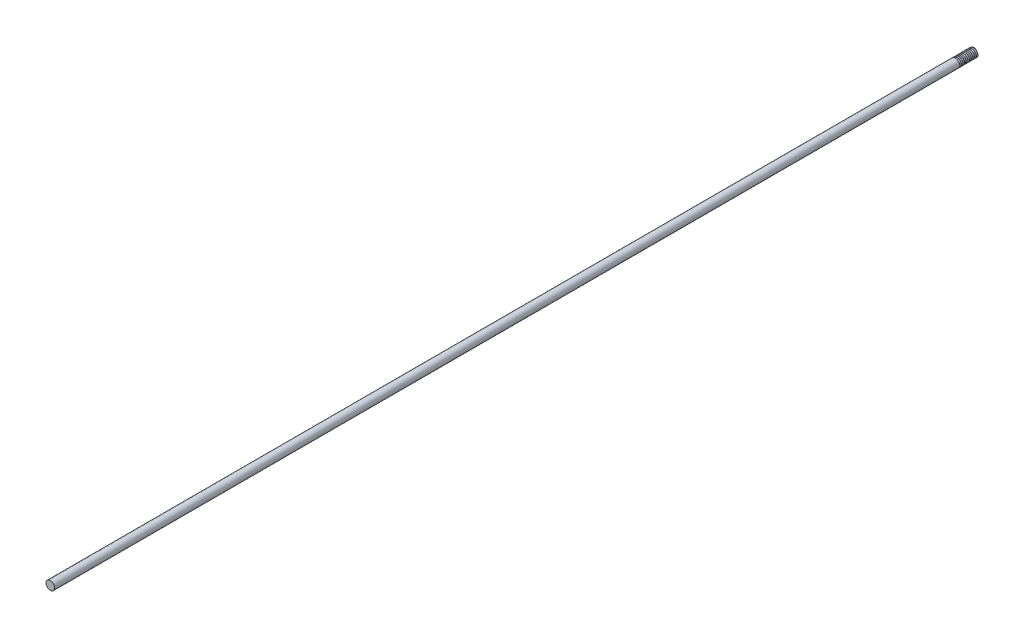
SolidWorks part; units mm, degrees
ref_plane "Front Plane" through (0, 0, 0) normal (0, 0, 1) x (1, 0, 0)
ref_plane "Top Plane" through (0, 0, 0) normal (0, 1, 0) x (1, 0, 0)
ref_plane "Right Plane" through (0, 0, 0) normal (1, 0, 0) x (0, 0, -1)
sketch "Sketch1" plane through (0, 0, 0) normal (0, 0, 1) x (1, 0, 0)
  circle A0 centre (0, 0) radius 1.1811
  dimension "D1" = 2.3622
extrude "Rod" add sketch "Sketch1" along normal blind 254
ref_plane "Plane1" through (0, 0, -1.27) normal (0, 0, -1) x (-1, 0, 0)
sketch "Sketch3" plane through (0, 0, -1.27) normal (0, 0, -1) x (-1, 0, 0)
  circle A0 centre (0, 0) radius 1.1811 construction
  circle A1 centre (0, 0) radius 1.1811
curve "Helix/Spiral1" pitch 0.4536 height 6.35 radius 1.1811 centre (0, 0, -1.27) axis (0, 0, 1) start towards (0, 1, 0)
sketch "Sketch4" plane through (0, 0, 0) normal (1, 0, 0) x (0, 0, -1)
  line L0 (1.0433, 1.2302) -> (1.4967, 1.2302)
  line L1 (1.4967, 1.2302) -> (1.27, 0.8375)
  line L2 (1.27, 0.8375) -> (1.0433, 1.2302)
  line L3 (1.27, 0.8375) -> (1.27, 1.2302) construction
  spline S0 degree 3 poles (-75.4369, -1997.273) (3.0387, -191.216) (2.0286, 8.4213) (1.2133, 0.8569) (1.185, 0.4638) (1.1566, 0) (1.1283, -0.4638) (1.0999, -0.8569) (1.0716, -1.1196) (1.0432, -1.2118) (1.0149, -1.1196) (0.9865, -0.8569) (0.9582, -0.4638) (0.9298, 0) (0.9015, 0.4638) (0.8731, 0.8569) (0.8448, 1.1196) (0.8164, 1.2118) (0.7881, 1.1196) (0.7597, 0.8569) (0.7314, 0.4638) (0.703, 0) (0.6747, -0.4638) (0.6463, -0.8569) (0.618, -1.1196) (0.5896, -1.2118) (0.5613, -1.1196) (0.5329, -0.8569) (0.5046, -0.4638) (0.4763, 0) (0.4479, 0.4638) (0.4196, 0.8569) (0.3912, 1.1196) (0.3629, 1.2118) (0.3345, 1.1196) (0.3062, 0.8569) (0.2778, 0.4638) (0.2495, 0) (0.2211, -0.4638) (0.1928, -0.8569) (0.1644, -1.1196) (0.1361, -1.2118) (0.1077, -1.1196) (0.0794, -0.8569) (0.051, -0.4638) (0.0227, 0) (-0.0057, 0.4638) (-0.034, 0.8569) (-0.0624, 1.1196) (-0.0907, 1.2118) (-0.1191, 1.1196) (-0.1474, 0.8569) (-0.1758, 0.4638) (-0.2041, 0) (-0.2325, -0.4638) (-0.2608, -0.8569) (-0.2892, -1.1196) (-0.3175, -1.2118) (-0.3458, -1.1196) (-0.3742, -0.8569) (-0.4025, -0.4638) (-0.4309, 0) (-0.4592, 0.4638) (-0.4876, 0.8569) (-0.5159, 1.1196) (-0.5443, 1.2118) (-0.5726, 1.1196) (-0.601, 0.8569) (-0.6293, 0.4638) (-0.6577, 0) (-0.686, -0.4638) (-0.7144, -0.8569) (-0.7427, -1.1196) (-0.7711, -1.2118) (-0.7994, -1.1196) (-0.8278, -0.8569) (-0.8561, -0.4638) (-0.8845, 0) (-0.9128, 0.4638) (-0.9412, 0.8569) (-0.9695, 1.1196) (-0.9979, 1.2118) (-1.0262, 1.1196) (-1.0546, 0.8569) (-1.0829, 0.4638) (-1.1112, 0) (-1.1396, -0.4638) (-1.1679, -0.8569) (-1.1963, -1.1196) (-1.2246, -1.2118) (-1.253, -1.1196) (-1.2813, -0.8569) (-1.3097, -0.4638) (-1.338, 0) (-1.3664, 0.4638) (-1.3947, 0.8569) (-1.4231, 1.1196) (-1.4514, 1.2118) (-1.4798, 1.1196) (-1.5081, 0.8569) (-1.5365, 0.4638) (-1.5648, 0) (-1.5932, -0.4638) (-1.6215, -0.8569) (-1.6499, -1.1196) (-1.6782, -1.2118) (-1.7066, -1.1196) (-1.7349, -0.8569) (-1.7633, -0.4638) (-1.7916, 0) (-1.82, 0.4638) (-1.8483, 0.8569) (-1.8767, 1.1196) (-1.905, 1.2118) (-1.9333, 1.1196) (-1.9617, 0.8569) (-1.99, 0.4638) (-2.0184, 0) (-2.0467, -0.4638) (-2.0751, -0.8569) (-2.1034, -1.1196) (-2.1318, -1.2118) (-2.1601, -1.1196) (-2.1885, -0.8569) (-2.2168, -0.4638) (-2.2452, 0) (-2.2735, 0.4638) (-2.3019, 0.8569) (-2.3302, 1.1196) (-2.3586, 1.2118) (-2.3869, 1.1196) (-2.4153, 0.8569) (-2.4436, 0.4638) (-2.472, 0) (-2.5003, -0.4638) (-2.5287, -0.8569) (-2.557, -1.1196) (-2.5854, -1.2118) (-2.6137, -1.1196) (-2.6421, -0.8569) (-2.6704, -0.4638) (-2.6987, 0) (-2.7271, 0.4638) (-2.7554, 0.8569) (-2.7838, 1.1196) (-2.8121, 1.2118) (-2.8405, 1.1196) (-2.8688, 0.8569) (-2.8972, 0.4638) (-2.9255, 0) (-2.9539, -0.4638) (-2.9822, -0.8569) (-3.0106, -1.1196) (-3.0389, -1.2118) (-3.0673, -1.1196) (-3.0956, -0.8569) (-3.124, -0.4638) (-3.1523, 0) (-3.1807, 0.4638) (-3.209, 0.8569) (-3.2374, 1.1196) (-3.2657, 1.2118) (-3.2941, 1.1196) (-3.3224, 0.8569) (-3.3508, 0.4638) (-3.3791, 0) (-3.4075, -0.4638) (-3.4358, -0.8569) (-3.4642, -1.1196) (-3.4925, -1.2118) (-3.5208, -1.1196) (-3.5492, -0.8569) (-3.5775, -0.4638) (-3.6059, 0) (-3.6342, 0.4638) (-3.6626, 0.8569) (-3.6909, 1.1196) (-3.7193, 1.2118) (-3.7476, 1.1196) (-3.776, 0.8569) (-3.8043, 0.4638) (-3.8327, 0) (-3.861, -0.4638) (-3.8894, -0.8569) (-3.9177, -1.1196) (-3.9461, -1.2118) (-3.9744, -1.1196) (-4.0028, -0.8569) (-4.0311, -0.4638) (-4.0595, 0) (-4.0878, 0.4638) (-4.1162, 0.8569) (-4.1445, 1.1196) (-4.1729, 1.2118) (-4.2012, 1.1196) (-4.2296, 0.8569) (-4.2579, 0.4638) (-4.2862, 0) (-4.3146, -0.4638) (-4.3429, -0.8569) (-4.3713, -1.1196) (-4.3996, -1.2118) (-4.428, -1.1196) (-4.4563, -0.8569) (-4.4847, -0.4638) (-4.513, 0) (-4.5414, 0.4638) (-4.5697, 0.8569) (-4.5981, 1.1196) (-4.6264, 1.2118) (-4.6548, 1.1196) (-4.6831, 0.8569) (-4.7115, 0.4638) (-4.7398, 0) (-4.7682, -0.4638) (-4.7965, -0.8569) (-4.8249, -1.1196) (-4.8532, -1.2118) (-4.8816, -1.1196) (-4.9099, -0.8569) (-4.9383, -0.4638) (-4.9666, 0) (-4.995, 0.4638) (-5.0233, 0.8569) (-5.8386, 8.4211) (-6.8487, -191.2103) (71.6235, -1997.1954) knots -0.372256 -0.372256 -0.372256 -0.372256 0.004464 0.008929 0.013393 0.017857 0.022321 0.026786 0.03125 0.035714 0.040179 0.044643 0.049107 0.053571 0.058036 0.0625 0.066964 0.071429 0.075893 0.080357 0.084821 0.089286 0.09375 0.098214 0.102679 0.107143 0.111607 0.116071 0.120536 0.125 0.129464 0.133929 0.138393 0.142857 0.147321 0.151786 0.15625 0.160714 0.165179 0.169643 0.174107 0.178571 0.183036 0.1875 0.191964 0.196429 0.200893 0.205357 0.209821 0.214286 0.21875 0.223214 0.227679 0.232143 0.236607 0.241071 0.245536 0.25 0.254464 0.258929 0.263393 0.267857 0.272321 0.276786 0.28125 0.285714 0.290179 0.294643 0.299107 0.303571 0.308036 0.3125 0.316964 0.321429 0.325893 0.330357 0.334821 0.339286 0.34375 0.348214 0.352679 0.357143 0.361607 0.366071 0.370536 0.375 0.379464 0.383929 0.388393 0.392857 0.397321 0.401786 0.40625 0.410714 0.415179 0.419643 0.424107 0.428571 0.433036 0.4375 0.441964 0.446429 0.450893 0.455357 0.459821 0.464286 0.46875 0.473214 0.477679 0.482143 0.486607 0.491071 0.495536 0.5 0.504464 0.508929 0.513393 0.517857 0.522321 0.526786 0.53125 0.535714 0.540179 0.544643 0.549107 0.553571 0.558036 0.5625 0.566964 0.571429 0.575893 0.580357 0.584821 0.589286 0.59375 0.598214 0.602679 0.607143 0.611607 0.616071 0.620536 0.625 0.629464 0.633929 0.638393 0.642857 0.647321 0.651786 0.65625 0.660714 0.665179 0.669643 0.674107 0.678571 0.683036 0.6875 0.691964 0.696429 0.700893 0.705357 0.709821 0.714286 0.71875 0.723214 0.727679 0.732143 0.736607 0.741071 0.745536 0.75 0.754464 0.758929 0.763393 0.767857 0.772321 0.776786 0.78125 0.785714 0.790179 0.794643 0.799107 0.803571 0.808036 0.8125 0.816964 0.821429 0.825893 0.830357 0.834821 0.839286 0.84375 0.848214 0.852679 0.857143 0.861607 0.866071 0.870536 0.875 0.879464 0.883929 0.888393 0.892857 0.897321 0.901786 0.90625 0.910714 0.915179 0.919643 0.924107 0.928571 0.933036 0.9375 0.941964 0.946429 0.950893 0.955357 0.959821 0.964286 0.96875 0.973214 0.977679 0.982143 0.986607 0.991071 0.995536 1.37225 1.37225 1.37225 1.37225 only from (1.27, 1.1811) to (-5.08, 1.1811) construction
  spline S1 degree 3 poles (1.27, 1.1811) (1.2606, 1.1811) (1.2416, 1.1196) (1.2133, 0.8569) (1.185, 0.4638) (1.1566, 0) (1.1283, -0.4638) (1.0999, -0.8569) (1.0716, -1.1196) (1.0432, -1.2118) (1.0149, -1.1196) (0.9865, -0.8569) (0.9582, -0.4638) (0.9298, 0) (0.9015, 0.4638) (0.8731, 0.8569) (0.8448, 1.1196) (0.8164, 1.2118) (0.7881, 1.1196) (0.7597, 0.8569) (0.7314, 0.4638) (0.703, 0) (0.6747, -0.4638) (0.6463, -0.8569) (0.618, -1.1196) (0.5896, -1.2118) (0.5613, -1.1196) (0.5329, -0.8569) (0.5046, -0.4638) (0.4763, 0) (0.4479, 0.4638) (0.4196, 0.8569) (0.3912, 1.1196) (0.3629, 1.2118) (0.3345, 1.1196) (0.3062, 0.8569) (0.2778, 0.4638) (0.2495, 0) (0.2211, -0.4638) (0.1928, -0.8569) (0.1644, -1.1196) (0.1361, -1.2118) (0.1077, -1.1196) (0.0794, -0.8569) (0.051, -0.4638) (0.0227, 0) (-0.0057, 0.4638) (-0.034, 0.8569) (-0.0624, 1.1196) (-0.0907, 1.2118) (-0.1191, 1.1196) (-0.1474, 0.8569) (-0.1758, 0.4638) (-0.2041, 0) (-0.2325, -0.4638) (-0.2608, -0.8569) (-0.2892, -1.1196) (-0.3175, -1.2118) (-0.3458, -1.1196) (-0.3742, -0.8569) (-0.4025, -0.4638) (-0.4309, 0) (-0.4592, 0.4638) (-0.4876, 0.8569) (-0.5159, 1.1196) (-0.5443, 1.2118) (-0.5726, 1.1196) (-0.601, 0.8569) (-0.6293, 0.4638) (-0.6577, 0) (-0.686, -0.4638) (-0.7144, -0.8569) (-0.7427, -1.1196) (-0.7711, -1.2118) (-0.7994, -1.1196) (-0.8278, -0.8569) (-0.8561, -0.4638) (-0.8845, 0) (-0.9128, 0.4638) (-0.9412, 0.8569) (-0.9695, 1.1196) (-0.9979, 1.2118) (-1.0262, 1.1196) (-1.0546, 0.8569) (-1.0829, 0.4638) (-1.1112, 0) (-1.1396, -0.4638) (-1.1679, -0.8569) (-1.1963, -1.1196) (-1.2246, -1.2118) (-1.253, -1.1196) (-1.2813, -0.8569) (-1.3097, -0.4638) (-1.338, 0) (-1.3664, 0.4638) (-1.3947, 0.8569) (-1.4231, 1.1196) (-1.4514, 1.2118) (-1.4798, 1.1196) (-1.5081, 0.8569) (-1.5365, 0.4638) (-1.5648, 0) (-1.5932, -0.4638) (-1.6215, -0.8569) (-1.6499, -1.1196) (-1.6782, -1.2118) (-1.7066, -1.1196) (-1.7349, -0.8569) (-1.7633, -0.4638) (-1.7916, 0) (-1.82, 0.4638) (-1.8483, 0.8569) (-1.8767, 1.1196) (-1.905, 1.2118) (-1.9333, 1.1196) (-1.9617, 0.8569) (-1.99, 0.4638) (-2.0184, 0) (-2.0467, -0.4638) (-2.0751, -0.8569) (-2.1034, -1.1196) (-2.1318, -1.2118) (-2.1601, -1.1196) (-2.1885, -0.8569) (-2.2168, -0.4638) (-2.2452, 0) (-2.2735, 0.4638) (-2.3019, 0.8569) (-2.3302, 1.1196) (-2.3586, 1.2118) (-2.3869, 1.1196) (-2.4153, 0.8569) (-2.4436, 0.4638) (-2.472, 0) (-2.5003, -0.4638) (-2.5287, -0.8569) (-2.557, -1.1196) (-2.5854, -1.2118) (-2.6137, -1.1196) (-2.6421, -0.8569) (-2.6704, -0.4638) (-2.6987, 0) (-2.7271, 0.4638) (-2.7554, 0.8569) (-2.7838, 1.1196) (-2.8121, 1.2118) (-2.8405, 1.1196) (-2.8688, 0.8569) (-2.8972, 0.4638) (-2.9255, 0) (-2.9539, -0.4638) (-2.9822, -0.8569) (-3.0106, -1.1196) (-3.0389, -1.2118) (-3.0673, -1.1196) (-3.0956, -0.8569) (-3.124, -0.4638) (-3.1523, 0) (-3.1807, 0.4638) (-3.209, 0.8569) (-3.2374, 1.1196) (-3.2657, 1.2118) (-3.2941, 1.1196) (-3.3224, 0.8569) (-3.3508, 0.4638) (-3.3791, 0) (-3.4075, -0.4638) (-3.4358, -0.8569) (-3.4642, -1.1196) (-3.4925, -1.2118) (-3.5208, -1.1196) (-3.5492, -0.8569) (-3.5775, -0.4638) (-3.6059, 0) (-3.6342, 0.4638) (-3.6626, 0.8569) (-3.6909, 1.1196) (-3.7193, 1.2118) (-3.7476, 1.1196) (-3.776, 0.8569) (-3.8043, 0.4638) (-3.8327, 0) (-3.861, -0.4638) (-3.8894, -0.8569) (-3.9177, -1.1196) (-3.9461, -1.2118) (-3.9744, -1.1196) (-4.0028, -0.8569) (-4.0311, -0.4638) (-4.0595, 0) (-4.0878, 0.4638) (-4.1162, 0.8569) (-4.1445, 1.1196) (-4.1729, 1.2118) (-4.2012, 1.1196) (-4.2296, 0.8569) (-4.2579, 0.4638) (-4.2862, 0) (-4.3146, -0.4638) (-4.3429, -0.8569) (-4.3713, -1.1196) (-4.3996, -1.2118) (-4.428, -1.1196) (-4.4563, -0.8569) (-4.4847, -0.4638) (-4.513, 0) (-4.5414, 0.4638) (-4.5697, 0.8569) (-4.5981, 1.1196) (-4.6264, 1.2118) (-4.6548, 1.1196) (-4.6831, 0.8569) (-4.7115, 0.4638) (-4.7398, 0) (-4.7682, -0.4638) (-4.7965, -0.8569) (-4.8249, -1.1196) (-4.8532, -1.2118) (-4.8816, -1.1196) (-4.9099, -0.8569) (-4.9383, -0.4638) (-4.9666, 0) (-4.995, 0.4638) (-5.0233, 0.8569) (-5.0516, 1.1196) (-5.0706, 1.1811) (-5.08, 1.1811) knots 0 0 0 0 0.004464 0.008929 0.013393 0.017857 0.022321 0.026786 0.03125 0.035714 0.040179 0.044643 0.049107 0.053571 0.058036 0.0625 0.066964 0.071429 0.075893 0.080357 0.084821 0.089286 0.09375 0.098214 0.102679 0.107143 0.111607 0.116071 0.120536 0.125 0.129464 0.133929 0.138393 0.142857 0.147321 0.151786 0.15625 0.160714 0.165179 0.169643 0.174107 0.178571 0.183036 0.1875 0.191964 0.196429 0.200893 0.205357 0.209821 0.214286 0.21875 0.223214 0.227679 0.232143 0.236607 0.241071 0.245536 0.25 0.254464 0.258929 0.263393 0.267857 0.272321 0.276786 0.28125 0.285714 0.290179 0.294643 0.299107 0.303571 0.308036 0.3125 0.316964 0.321429 0.325893 0.330357 0.334821 0.339286 0.34375 0.348214 0.352679 0.357143 0.361607 0.366071 0.370536 0.375 0.379464 0.383929 0.388393 0.392857 0.397321 0.401786 0.40625 0.410714 0.415179 0.419643 0.424107 0.428571 0.433036 0.4375 0.441964 0.446429 0.450893 0.455357 0.459821 0.464286 0.46875 0.473214 0.477679 0.482143 0.486607 0.491071 0.495536 0.5 0.504464 0.508929 0.513393 0.517857 0.522321 0.526786 0.53125 0.535714 0.540179 0.544643 0.549107 0.553571 0.558036 0.5625 0.566964 0.571429 0.575893 0.580357 0.584821 0.589286 0.59375 0.598214 0.602679 0.607143 0.611607 0.616071 0.620536 0.625 0.629464 0.633929 0.638393 0.642857 0.647321 0.651786 0.65625 0.660714 0.665179 0.669643 0.674107 0.678571 0.683036 0.6875 0.691964 0.696429 0.700893 0.705357 0.709821 0.714286 0.71875 0.723214 0.727679 0.732143 0.736607 0.741071 0.745536 0.75 0.754464 0.758929 0.763393 0.767857 0.772321 0.776786 0.78125 0.785714 0.790179 0.794643 0.799107 0.803571 0.808036 0.8125 0.816964 0.821429 0.825893 0.830357 0.834821 0.839286 0.84375 0.848214 0.852679 0.857143 0.861607 0.866071 0.870536 0.875 0.879464 0.883929 0.888393 0.892857 0.897321 0.901786 0.90625 0.910714 0.915179 0.919643 0.924107 0.928571 0.933036 0.9375 0.941964 0.946429 0.950893 0.955357 0.959821 0.964286 0.96875 0.973214 0.977679 0.982143 0.986607 0.991071 0.995536 1 1 1 1 construction
  point P2 (1.27, 1.1811)
  dimension "D1" = 60
  dimension "D2" = 0.4534
  dimension "D3" = 0.3926
  dimension "D4" = 0.0491
sweep "Cut-Sweep1" cut profiles "Sketch4" path "Helix/Spiral1"
sketch "Sketch5" plane through (0, 0, 0) normal (1, 0, 0) x (0, 0, -1)
  line L3 (-5.2784, 1.1811) -> (-5.08, 0.8375)
  line L4 (-5.08, 0.8375) -> (-4.8816, 1.1811)
  line L5 (-4.8816, 1.1811) -> (-5.2784, 1.1811)
  line L6 (-5.2784, 1.1811) -> (-5.08, 0.8375)
  line L7 (-5.08, 0.8375) -> (-4.8816, 1.1811)
  line L8 (-4.8816, 1.1811) -> (-5.2784, 1.1811)
  dimension "D1" = 0
extrude "Cut-Extrude1" cut sketch "Sketch5" against normal through all
